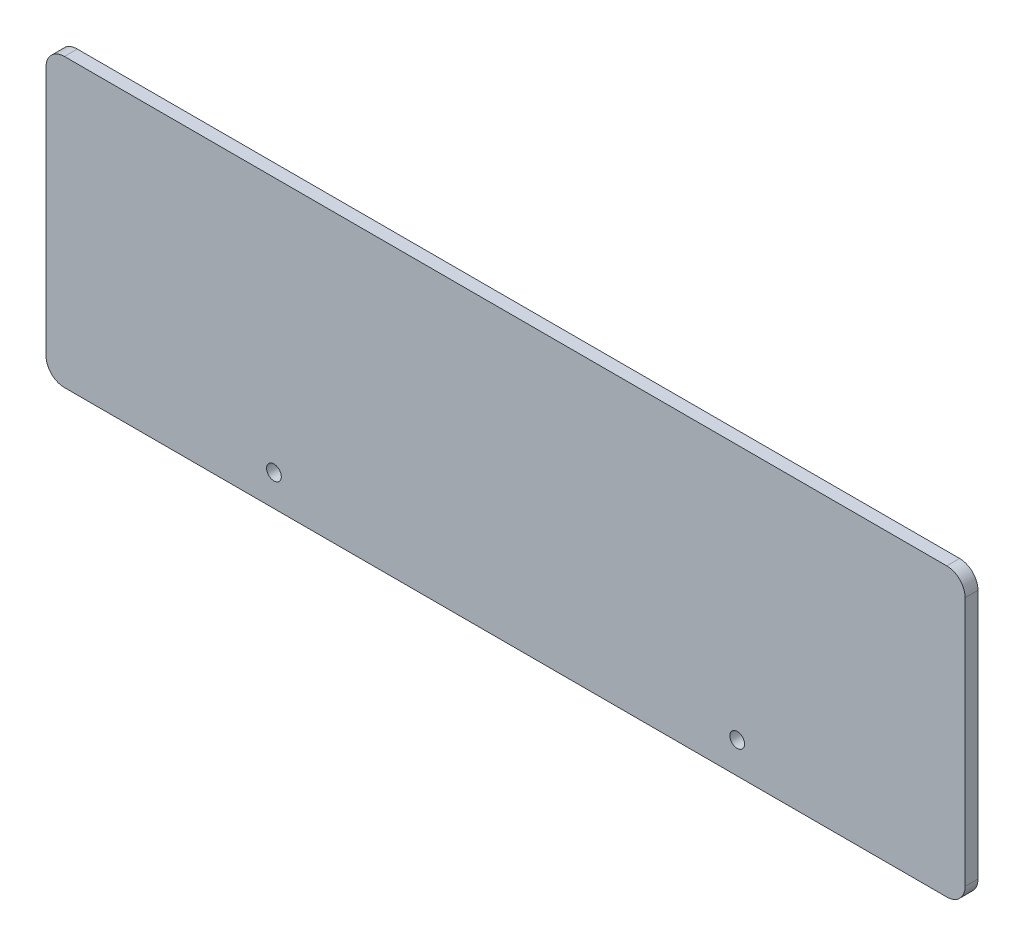
SolidWorks part; units mm, degrees
ref_plane "Plan de face" through (0, 0, 0) normal (0, 0, 1) x (1, 0, 0)
ref_plane "Plan de dessus" through (0, 0, 0) normal (0, 1, 0) x (1, 0, 0)
ref_plane "Plan de droite" through (0, 0, 0) normal (1, 0, 0) x (0, 0, -1)
sketch "Esquisse1" plane through (0, 0, 0) normal (0, 0, 1) x (1, 0, 0)
  line L1 (5, 0) -> (245, 0)
  line L2 (0, 5) -> (0, 73)
  line L3 (5, 78) -> (245, 78)
  line L4 (250, 5) -> (250, 73)
  arc A0 (250, 5) -> (245, 0) centre (245, 5) cw
  arc A1 (250, 73) -> (245, 78) centre (245, 73) ccw
  arc A2 (5, 0) -> (0, 5) centre (5, 5) cw
  arc A3 (5, 78) -> (0, 73) centre (5, 73) ccw
  point P9 (250, 78)
  point P12 (0, 0)
  point P15 (0, 78)
  dimension "D3" = 5
  dimension "D1" = 250
  dimension "D2" = 78
extrude "Boss.-Extru.1" add sketch "Esquisse1" along normal blind 3.5
sketch "Esquisse2" plane through (0, 0, 3.5) normal (0, 0, 1) x (1, 0, 0)
  line L0 (-35.7922, 8.5) -> (305.0105, 8.5) construction
  line L1 (5, 0) -> (245, 0) construction
  line L2 (0, 73) -> (0, 5) construction
  circle A0 centre (62, 8.5) radius 2
  circle A1 centre (188, 8.5) radius 2
  dimension "D2" = 4
  dimension "D5" = 4
  dimension "D1" = 8.5
  dimension "D3" = 62
  dimension "D4" = 126
extrude "Enlèv. mat.-Extru.1" cut sketch "Esquisse2" against normal through all
